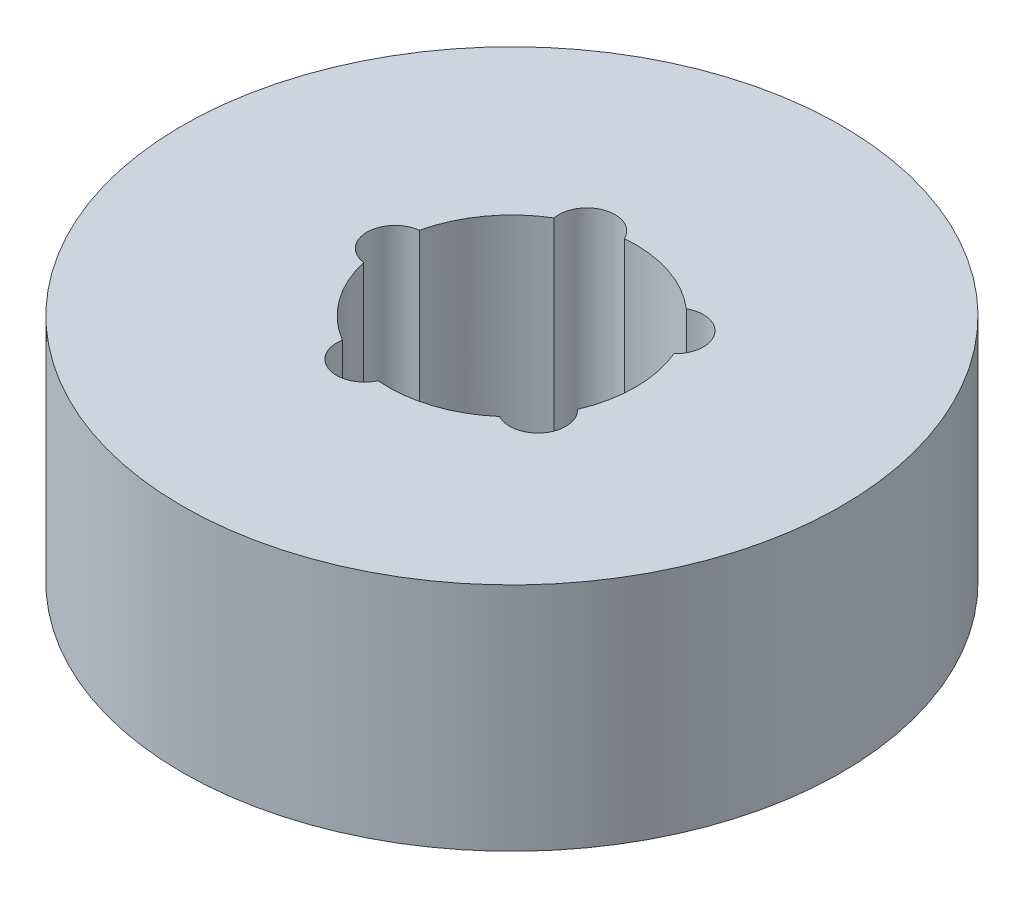
SolidWorks part; units mm, degrees
ref_plane "Front Plane" through (0, 0, 0) normal (0, 0, 1) x (1, 0, 0)
ref_plane "Top Plane" through (0, 0, 0) normal (0, 1, 0) x (1, 0, 0)
ref_plane "Right Plane" through (0, 0, 0) normal (1, 0, 0) x (0, 0, -1)
sketch "Sketch1" plane through (0, 0, 0) normal (0, 1, 0) x (1, 0, 0)
  circle A0 centre (0, 0) radius 40
  dimension "FLANGE_OD" = 80
extrude "Boss-Extrude1" add sketch "Sketch1" along normal blind 28
sketch "Sketch2" plane through (0, 0, 0) normal (0, 1, 0) x (1, 0, 0)
  circle A0 centre (0, 0) radius 15
  dimension "BORE_D" = 30
extrude "Cut-Extrude1" cut sketch "Sketch2" along normal through all
sketch "Sketch3" plane through (0, 28, 0) normal (0, 1, 0) x (1, 0, 0)
  circle A0 centre (0, 0) radius 14.1904 construction
  circle A1 centre (-14.1904, 0) radius 3.4108
  dimension "BOLT_D" = 6.8217
  dimension "BOLT_PCD" = 28.3809
extrude "Cut-Extrude2" cut sketch "Sketch3" against normal blind 23.8998
pattern_circular "CirPattern1" count 5 over 360 about axis through (0, 0, 0) along (0, 1, 0) of "Cut-Extrude2"
